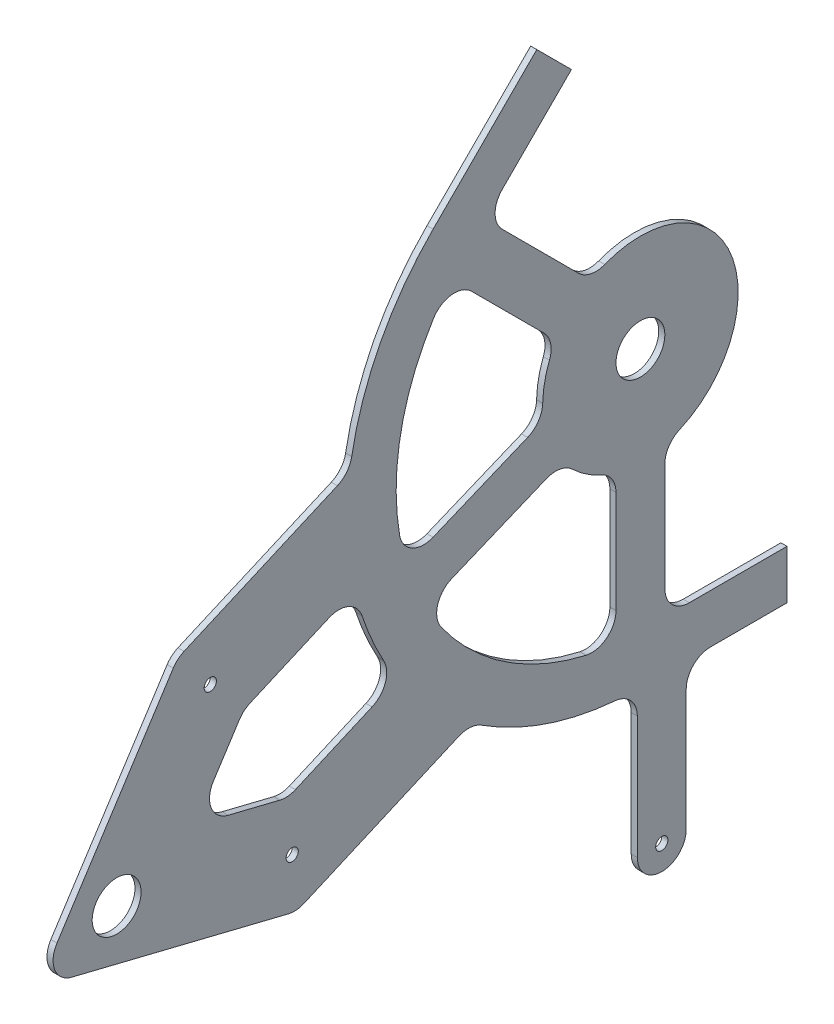
SolidWorks part; units mm, degrees
ref_plane "Front Plane" through (0, 0, 0) normal (0, 0, 1) x (1, 0, 0)
ref_plane "Top Plane" through (0, 0, 0) normal (0, 1, 0) x (1, 0, 0)
ref_plane "Right Plane" through (0, 0, 0) normal (1, 0, 0) x (0, 0, -1)
sketch "Sketch8" plane through (0, 0, 0) normal (1, 0, 0) x (0, 0, -1)
  line L0 (0, 0) -> (-139.7, 0) construction
  circle A1 centre (-272.2355, -114.6296) radius 12.7
  circle A3 centre (-223.5488, -39.2772) radius 3.175
  circle A5 centre (-180.9898, -137.1562) radius 3.175
  circle A7 centre (0, 0) radius 12.7
  circle A9 centre (11.1033, -228.1813) radius 3.175
  circle A10 centre (0, 0) radius 336.7856
  circle A11 centre (0, 0) radius 127
  circle A12 centre (0, 0) radius 152.4
sketch "Sketch9" plane through (0, 0, 0) normal (1, 0, 0) x (0, 0, -1)
  line L0 (0, -126.9544) -> (0, -152.3905)
  line L1 (-89.7703, 89.7703) -> (-107.7564, 107.7564) construction
  line L2 (-98.7633, 98.7633) -> (-44.8818, 152.6449) construction
  line L3 (-107.7564, 107.7564) -> (-53.8406, 161.6722)
  line L4 (-53.8406, 161.6722) -> (-35.8545, 143.6861)
  line L5 (-35.8545, 143.6861) -> (-89.7703, 89.7703)
  arc A0 (-107.7564, 107.7564) -> (0, -152.3905) centre (0, 0) ccw
  arc A1 (-89.7703, 89.7703) -> (0, -126.9544) centre (0, 0) ccw
extrude "Boss-Extrude2" add sketch "Sketch9" along normal blind 3.175
sketch "Sketch11" plane through (0, 0, 0) normal (1, 0, 0) x (0, 0, -1)
  line L0 (0, -152.3905) -> (0, -126.9544) construction
  line L1 (0, -152.3905) -> (0, -126.9544)
  line L2 (0, -126.9544) -> (76.2, -126.9544)
  line L3 (76.2, -126.9544) -> (76.2, -152.3905)
  line L4 (76.2, -152.3905) -> (0, -152.3905)
extrude "Boss-Extrude4" add sketch "Sketch11" along normal blind 3.175
sketch "Sketch12" plane through (0, 0, 0) normal (1, 0, 0) x (0, 0, -1)
  line L0 (11.1033, -228.1813) -> (11.1033, -152.3905) construction
  line L1 (0, -152.3905) -> (76.2, -152.3905) construction
  line L2 (23.8033, -228.1813) -> (23.8033, -152.3905)
  line L3 (-1.5967, -228.1813) -> (-1.5967, -152.3822)
  line L4 (0, -152.3905) -> (23.8033, -152.3905)
  line L5 (-1.5967, -228.1813) -> (-1.5967, -152.3905) construction
  circle A0 centre (11.1033, -228.1813) radius 3.175 construction
  circle A1 centre (11.1033, -228.1813) radius 3.175
  arc A2 (-107.7564, 107.7564) -> (0, -152.3905) centre (0, 0) ccw construction
  arc A3 (-1.5967, -152.3822) -> (0, -152.3905) centre (0, 0) ccw
  arc A4 (23.8033, -228.1813) -> (-1.5717, -227.3844) centre (11.1033, -228.1813) cw
extrude "Boss-Extrude5" add sketch "Sketch12" along normal blind 3.175 contours A4 L2 L4 A3 L3 A1 region at (0, -194.8352, -11.1033)
sketch "Sketch13" plane through (0, 0, 0) normal (1, 0, 0) x (0, 0, -1)
  line L0 (-223.5488, -39.2772) -> (-152.1684, -8.2246) construction
  line L1 (-180.9898, -137.1562) -> (-109.4511, -106.0346) construction
  line L2 (-180.9898, -137.1562) -> (-272.2355, -114.6296) construction
  line L3 (-272.2355, -114.6296) -> (-223.5488, -39.2772) construction
  line L4 (-272.2355, -114.6296) -> (-141.0941, -57.5789) construction
  line L5 (-179.3041, -108.7234) -> (-126.0941, -85.5754)
  line L6 (-187.4143, -109.4075) -> (-214.2907, -102.7723)
  line L7 (-221.9139, -83.5503) -> (-208.4616, -62.7302)
  line L8 (-202.8607, -57.9767) -> (-148.4762, -34.3177)
  line L9 (-174.7967, -162.1614) -> (-88.0105, -124.4067)
  line L10 (-182.9069, -162.8455) -> (-295.6091, -135.0218)
  line L11 (-303.2322, -115.7997) -> (-242.8006, -22.2699)
  line L12 (-237.1998, -17.5164) -> (-151.0792, 19.9487)
  line L13 (-240.7183, -19.0471) -> (-162.301, 15.0669) construction
  line L14 (-178.7361, -163.8752) -> (-99.3186, -129.3261) construction
  line L15 (-206.3792, -59.5074) -> (-142.0359, -31.516) construction
  line L16 (-183.2435, -110.4372) -> (-119.5836, -82.7431) construction
  line L17 (-312.8947, -130.7543) -> (-240.7183, -19.0471) construction
  line L18 (-178.7361, -163.8752) -> (-312.8947, -130.7543) construction
  line L19 (-183.2435, -110.4372) -> (-231.5763, -98.5049) construction
  line L20 (-231.5763, -98.5049) -> (-206.3792, -59.5074) construction
  circle A0 centre (-180.9898, -137.1562) radius 3.175 construction
  circle A1 centre (-272.2355, -114.6296) radius 12.7 construction
  circle A2 centre (-223.5488, -39.2772) radius 3.175 construction
  circle A3 centre (-180.9898, -137.1562) radius 3.175
  circle A4 centre (-272.2355, -114.6296) radius 12.7
  circle A5 centre (-223.5488, -39.2772) radius 3.175
  arc A7 (-107.7564, 107.7564) -> (-1.5967, -152.3822) centre (0, 0) ccw construction
  arc A8 (-107.7564, 107.7564) -> (-1.5967, -152.3822) centre (0, 0) ccw construction
  arc A9 (-151.0792, 19.9487) -> (-148.4762, -34.3177) centre (0, 0) ccw
  arc A10 (-126.0941, -85.5754) -> (-88.0105, -124.4067) centre (0, 0) ccw
  arc A11 (-242.8006, -22.2699) -> (-237.1998, -17.5164) centre (-232.1335, -29.1622) cw
  arc A12 (-174.7967, -162.1614) -> (-182.9069, -162.8455) centre (-179.8629, -150.5157) cw
  arc A13 (-179.3041, -108.7234) -> (-187.4143, -109.4075) centre (-184.3703, -97.0777) cw
  arc A14 (-208.4616, -62.7302) -> (-202.8607, -57.9767) centre (-197.7945, -69.6225) cw
  arc A15 (-295.6091, -135.0218) -> (-303.2322, -115.7997) centre (-292.5651, -122.692) cw
  arc A16 (-214.2907, -102.7723) -> (-221.9139, -83.5503) centre (-211.2468, -90.4425) cw
  dimension "D1" = 12.7
extrude "Boss-Extrude6" add sketch "Sketch13" along normal blind 3.175
fillet "Fillet1" radius 12.7 6 edges at (1.5875, -34.3177, 148.4762) (1.5875, -85.5754, 126.0941) (1.5875, -124.4067, 88.0105) (1.5875, -152.3822, 1.5967) (1.5875, -152.3905, -23.8033) (1.5875, 19.9487, 151.0792)
sketch "Sketch14" plane through (0, 0, 0) normal (1, 0, 0) x (0, 0, -1)
  line L0 (0, 0) -> (-117.2906, -48.5833) construction
  line L1 (0, 0) -> (0, -126.9544) construction
  line L2 (0, 0) -> (-89.7703, 89.7703) construction
  line L3 (-25.8001, 43.7606) -> (-80.79, 98.7506)
  line L4 (76.2, -126.9544) -> (0, -126.9544) construction
  line L5 (12.7, -126.9544) -> (0, -126.9544)
  line L6 (-89.7703, 89.7703) -> (-35.8545, 143.6861) construction
  line L7 (-89.7703, 89.7703) -> (-80.79, 98.7506)
  line L8 (12.7, -49.1869) -> (12.7, -126.9544)
  line L9 (12.7, 0) -> (12.7, -126.9544) construction
  line L10 (-12.7, -49.1869) -> (-12.7, -126.3176)
  line L12 (-40.5827, -30.5563) -> (-111.8421, -60.0729)
  line L14 (-50.3028, -7.0897) -> (-121.5623, -36.6064)
  line L16 (-43.7606, 25.8001) -> (-98.3003, 80.3397)
  line L18 (8.9803, 8.9803) -> (-80.79, 98.7506) construction
  circle A0 centre (0, 0) radius 12.7 construction
  circle A1 centre (0, 0) radius 12.7
  arc A2 (-89.7703, 89.7703) -> (0, -126.9544) centre (0, 0) ccw construction
  arc A3 (-40.5827, -30.5563) -> (-12.7, -49.1869) centre (0, 0) ccw
  arc A4 (12.7, -49.1869) -> (-25.8001, 43.7606) centre (0, 0) ccw
  arc A5 (-43.7606, 25.8001) -> (-50.3028, -7.0897) centre (0, 0) ccw
  arc A6 (-89.7703, 89.7703) -> (-98.3003, 80.3397) centre (0, 0) ccw
  arc A7 (-121.5623, -36.6064) -> (-111.8421, -60.0729) centre (0, 0) ccw
  arc A8 (-12.7, -126.3176) -> (0, -126.9544) centre (0, 0) ccw
extrude "Boss-Extrude7" add sketch "Sketch14" along normal blind 3.175
fillet "Fillet2" radius 12.7 12 edges at (1.5875, -7.0897, 50.3028) (1.5875, 25.8001, 43.7606) (1.5875, 80.3397, 98.3003) (1.5875, -36.6064, 121.5623) (1.5875, -60.0729, 111.8421) (1.5875, -30.5563, 40.5827) (1.5875, -49.1869, 12.7) (1.5875, -126.3176, 12.7) (1.5875, -126.9544, -12.7) (1.5875, -49.1869, -12.7) (1.5875, 43.7606, 25.8001) (1.5875, 98.7506, 80.79)
